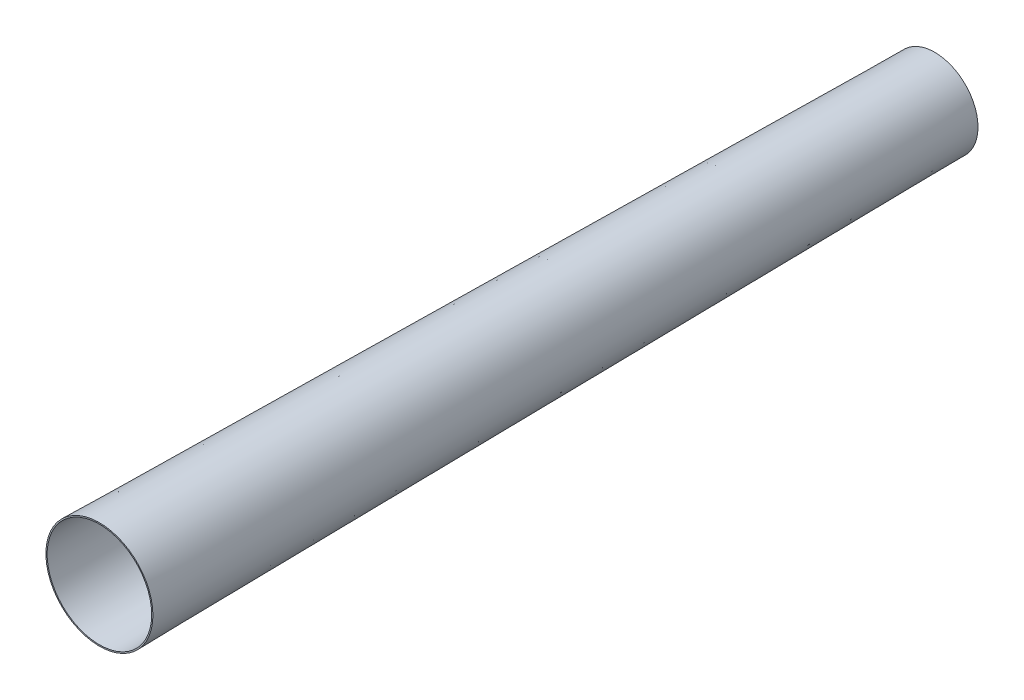
SolidWorks part; units mm, degrees
ref_plane "Front Plane" through (0, 0, 0) normal (0, 0, 1) x (1, 0, 0)
ref_plane "Top Plane" through (0, 0, 0) normal (0, 1, 0) x (1, 0, 0)
ref_plane "Right Plane" through (0, 0, 0) normal (1, 0, 0) x (0, 0, -1)
sketch "Sketch1" plane through (0, 0, 0) normal (0, 0, 1) x (1, 0, 0)
  circle A0 centre (0, 0) radius 16.8661
  circle A1 centre (0, 0) radius 17.3661
  dimension "D2" = 34.7323
  dimension "D1" = 0.5
ref_plane "Plane1" through (0, 0, 335.6419) normal (0, 0, 1) x (1, 0, 0)
sketch "Sketch2" plane through (0, 0, 335.6419) normal (0, 0, 1) x (1, 0, 0)
  circle A0 centre (0, 0) radius 21.5
  circle A1 centre (0, 0) radius 21
  dimension "D2" = 43
  dimension "D1" = 0.5
loft "Loft1" add section "Sketch1" section "Sketch2" start constraint default connector at (-15.7087, -7.404, 0) connector at (-19.4767, -9.1053, 335.6419)
shell "Shell1" thickness 0.5 removed face at (17.3661, 0, 0) removed face at (21.5, 0, 335.6419)
